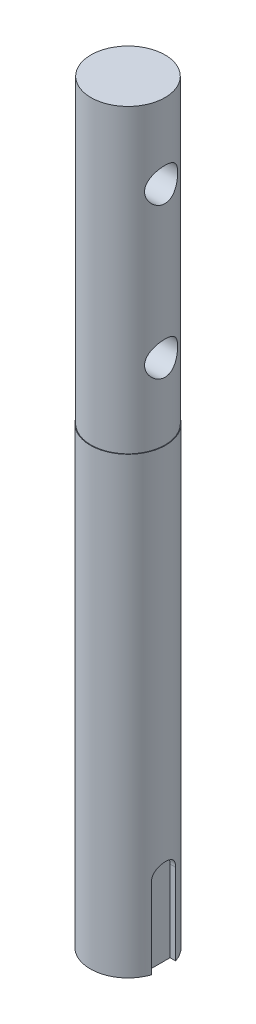
SolidWorks part; units mm, degrees
material "ASTM A36 Steel"
ref_plane "Front Plane" through (0, 0, 0) normal (0, 0, 1) x (1, 0, 0)
ref_plane "Top Plane" through (0, 0, 0) normal (0, 1, 0) x (1, 0, 0)
ref_plane "Right Plane" through (0, 0, 0) normal (1, 0, 0) x (0, 0, -1)
sketch "Sketch1" plane through (0, 0, 0) normal (0, 1, 0) x (1, 0, 0)
  circle A0 centre (0, 0) radius 25
  dimension "D1" = 50
extrude "Boss-Extrude1" add sketch "Sketch1" along normal blind 301.5
sketch "Sketch2" plane through (0, 301.5, 0) normal (0, 1, 0) x (1, 0, 0)
  circle A0 centre (0, 0) radius 24.61
  dimension "D1" = 49.22
extrude "Boss-Extrude2" add sketch "Sketch2" along normal blind 200
ref_plane "Plane1" through (25, 0, 0) normal (1, 0, 0) x (0, 0, -1)
sketch "Sketch3" plane through (25, 0, 0) normal (1, 0, 0) x (0, 0, -1)
  line L0 (-25, 0) -> (25, 0) construction
  line L1 (-8, 53.9) -> (-8, 0)
  line L2 (-8, 0) -> (8, 0)
  line L3 (8, 0) -> (8, 53.9)
  arc A0 (8, 53.9) -> (-8, 53.9) centre (0, 53.9) ccw
  dimension "D1" = 16
  dimension "D2" = 53.9
extrude "Cut-Extrude1" cut sketch "Sketch3" against normal blind 5
sketch "Sketch4" plane through (0, 0, 0) normal (1, 0, 0) x (0, 0, -1)
  line L0 (25, 301.5) -> (-25, 301.5) construction
  circle A0 centre (0, 351.5) radius 11
  circle A1 centre (0, 451.5) radius 11
  dimension "D1" = 22
  dimension "D2" = 22
  dimension "D3" = 50
  dimension "D4" = 100
extrude "Cut-Extrude2" cut sketch "Sketch4" against normal through all both and the other way through all
sketch "Sketch5" plane through (0, 0, 0) normal (0, -1, 0) x (-1, 0, 0)
  circle A0 centre (0, 0) radius 5
  dimension "D1" = 10
extrude "Cut-Extrude3" cut sketch "Sketch5" against normal blind 50
thread "Thread1" pitch 1.25 method cut profile "Thread Profile1" start angle 0, offset 0, length 47, pitch 1.25, diameter 10
ref_plane "Plane2" through (5, 0, 0) normal (0, 0, 1) x (1, 0, 0)
sketch "Thread Profile1" plane through (5, 0, 0) normal (0, 0, 1) x (1, 0, 0)
  line L0 (0, 0) -> (0, 1.25) construction
  line L1 (0, 0) -> (0.6766, 0.3906)
  line L2 (0.6766, 0.3906) -> (0.6766, 0.5469)
  line L3 (0.6766, 0.5469) -> (0, 0.9375)
  line L4 (0.6766, 0.4687) -> (0, 0.4687) construction
  line L11 (0, 0) -> (0, 0.9375)
  point P2 (0, 0)
  dimension "Pitch" = 1.25
  dimension "Profile_Angle" = 60
  dimension "Profile_Land" = 0.1562
  dimension "Profile_Height" = 0.6766
